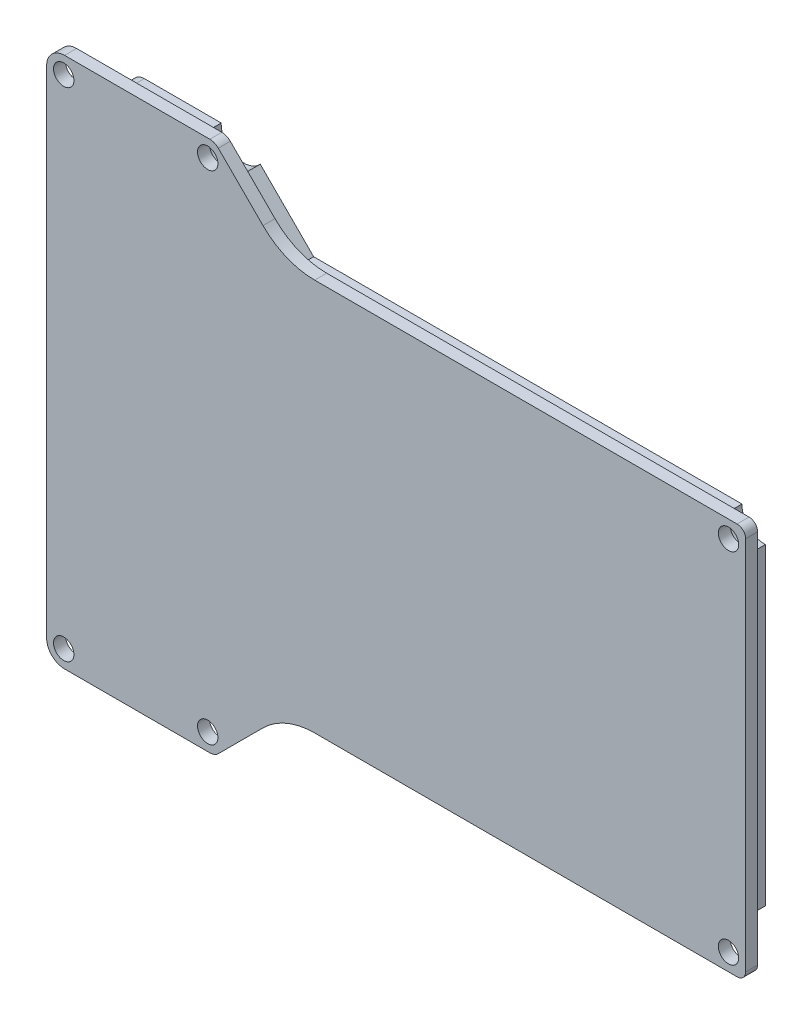
SolidWorks part; units mm, degrees
ref_plane "Front Plane" through (0, 0, 0) normal (0, 0, 1) x (1, 0, 0)
ref_plane "Top Plane" through (0, 0, 0) normal (0, 1, 0) x (1, 0, 0)
ref_plane "Right Plane" through (0, 0, 0) normal (1, 0, 0) x (0, 0, -1)
sketch "Sketch1" plane through (0, 0, 0) normal (0, 0, 1) x (1, 0, 0)
  line L8 (28.7801, -21.4985) -> (21.333, -14.0514)
  line L9 (107.834, -25.0706) -> (37.404, -25.0706)
  line L10 (109.259, -89.0386) -> (109.259, -26.4956)
  line L11 (37.409, -90.4636) -> (107.834, -90.4636)
  line L12 (21.333, -101.4878) -> (28.7851, -94.0357)
  line L13 (-4.3, -102.0736) -> (19.9188, -102.0736)
  line L14 (-7.3, -16.4656) -> (-7.3, -99.0736)
  line L15 (19.9188, -13.4656) -> (-4.3, -13.4656)
  line L16 (16.9123, -100.2696) -> (3, -100.2696) construction
  line L17 (0, -97.2696) -> (0, -18.2696) construction
  line L18 (31.61, -88.6596) -> (22.1833, -98.0863) construction
  line L19 (103.7528, -88.6596) -> (31.61, -88.6596) construction
  line L20 (107.455, -84.9574) -> (107.455, -30.5767) construction
  line L21 (31.605, -26.8746) -> (103.7528, -26.8746) construction
  line L22 (22.1833, -17.4529) -> (31.605, -26.8746) construction
  line L23 (3, -15.2696) -> (16.9123, -15.2696) construction
  line L24 (16.9123, -100.2696) -> (3, -100.2696)
  line L25 (0, -97.2696) -> (0, -18.2696)
  line L26 (31.61, -88.6596) -> (22.1833, -98.0863)
  line L27 (103.7528, -88.6596) -> (31.61, -88.6596)
  line L28 (107.455, -84.9574) -> (107.455, -30.5767)
  line L29 (31.605, -26.8746) -> (103.7528, -26.8746)
  line L30 (22.1833, -17.4529) -> (31.605, -26.8746)
  line L31 (3, -15.2696) -> (16.9123, -15.2696)
  line L32 (3, -16.1696) -> (15.8154, -16.1696)
  line L33 (22.3225, -18.8649) -> (31.2322, -27.7746)
  line L34 (31.2322, -27.7746) -> (102.656, -27.7746)
  line L35 (106.555, -83.8606) -> (106.555, -31.6736)
  line L36 (102.656, -87.7596) -> (31.2372, -87.7596)
  line L37 (31.2372, -87.7596) -> (22.3225, -96.6743)
  line L38 (15.8154, -99.3696) -> (3, -99.3696)
  line L39 (0.9, -97.2696) -> (0.9, -18.2696)
  line L40 (90.115, -68.9796) -> (22, -68.9796) construction
  line L41 (90.115, -44.8746) -> (22, -44.8746) construction
  line L42 (90.115, -68.9796) -> (22, -68.9796) construction
  line L43 (90.115, -44.8746) -> (22, -44.8746) construction
  line L44 (22, -68.9796) -> (0.9, -68.9796) construction
  line L45 (22, -44.8746) -> (0.9, -44.8746) construction
  line L46 (90.115, -44.8746) -> (106.555, -44.8746) construction
  line L47 (90.115, -68.9796) -> (106.555, -68.9796) construction
  line L48 (90.115, -44.3746) -> (104.755, -44.3746)
  line L49 (90.115, -44.3746) -> (22, -44.3746)
  line L50 (22, -44.3746) -> (2.7, -44.3746)
  line L51 (90.115, -69.4796) -> (104.755, -69.4796)
  line L52 (90.115, -69.4796) -> (22, -69.4796)
  line L53 (22, -69.4796) -> (2.7, -69.4796)
  line L54 (90.115, -71.2796) -> (104.755, -71.2796)
  line L55 (90.115, -71.2796) -> (22, -71.2796)
  line L56 (22, -71.2796) -> (2.7, -71.2796)
  line L57 (90.115, -42.5746) -> (104.755, -42.5746)
  line L58 (90.115, -42.5746) -> (22, -42.5746)
  line L59 (22, -42.5746) -> (2.7, -42.5746)
  line L60 (3, -17.9696) -> (14.2636, -17.9696)
  line L61 (22.1471, -21.235) -> (30.4866, -29.5746)
  line L62 (30.4866, -29.5746) -> (101.1041, -29.5746)
  line L63 (104.755, -82.3087) -> (104.755, -71.2796)
  line L64 (101.1041, -85.9596) -> (30.4916, -85.9596)
  line L65 (30.4916, -85.9596) -> (22.1471, -94.3042)
  line L66 (14.2636, -97.5696) -> (3, -97.5696)
  line L67 (2.7, -97.2696) -> (2.7, -71.2796)
  line L68 (104.755, -69.4796) -> (104.755, -44.3746)
  line L69 (104.755, -42.5746) -> (104.755, -33.2255)
  line L70 (104.755, -82.3087) -> (104.755, -33.2255) construction
  line L71 (90.115, -71.2796) -> (106.555, -71.2796) construction
  line L72 (90.115, -69.4796) -> (106.555, -69.4796) construction
  line L73 (90.115, -44.3746) -> (106.555, -44.3746) construction
  line L74 (2.7, -42.5746) -> (2.7, -18.2696)
  line L75 (90.115, -42.5746) -> (106.555, -42.5746) construction
  line L76 (22, -44.3746) -> (0.9, -44.3746) construction
  line L77 (2.7, -69.4796) -> (2.7, -44.3746)
  line L78 (2.7, -97.2696) -> (2.7, -18.2696) construction
  line L79 (22, -42.5746) -> (0.9, -42.5746) construction
  line L80 (22, -71.2796) -> (0.9, -71.2796) construction
  line L82 (22, -69.4796) -> (0.9, -69.4796) construction
  arc A8 (21.333, -14.0514) -> (19.9188, -13.4656) centre (19.9188, -15.4656) ccw
  arc A9 (28.7801, -21.4985) -> (37.404, -25.0706) centre (37.404, -12.8746) ccw
  arc A10 (109.259, -26.4956) -> (107.834, -25.0706) centre (107.834, -26.4956) ccw
  arc A11 (107.834, -90.4636) -> (109.259, -89.0386) centre (107.834, -89.0386) ccw
  arc A12 (37.409, -90.4636) -> (28.7851, -94.0357) centre (37.409, -102.6596) ccw
  arc A13 (19.9188, -102.0736) -> (21.333, -101.4878) centre (19.9188, -100.0736) ccw
  arc A14 (-7.3, -99.0736) -> (-4.3, -102.0736) centre (-4.3, -99.0736) ccw
  arc A15 (-4.3, -13.4656) -> (-7.3, -16.4656) centre (-4.3, -16.4656) ccw
  arc A16 (22.1833, -98.0863) -> (16.9123, -100.2696) centre (19.5655, -99.2206) ccw construction
  arc A17 (0, -97.2696) -> (3, -100.2696) centre (3, -97.2696) ccw construction
  arc A18 (107.455, -84.9574) -> (103.7528, -88.6596) centre (106.406, -87.6106) ccw construction
  arc A19 (103.7528, -26.8746) -> (107.455, -30.5767) centre (106.406, -27.9236) ccw construction
  arc A26 (16.9123, -15.2696) -> (22.1833, -17.4529) centre (19.5655, -16.3186) ccw construction
  arc A27 (3, -15.2696) -> (0, -18.2696) centre (3, -18.2696) ccw construction
  arc A28 (22.1833, -98.0863) -> (16.9123, -100.2696) centre (19.5655, -99.2206) ccw
  arc A29 (0, -97.2696) -> (3, -100.2696) centre (3, -97.2696) ccw
  arc A30 (107.455, -84.9574) -> (103.7528, -88.6596) centre (106.406, -87.6106) ccw
  arc A31 (103.7528, -26.8746) -> (107.455, -30.5767) centre (106.406, -27.9236) ccw
  arc A32 (16.9123, -15.2696) -> (22.1833, -17.4529) centre (19.5655, -16.3186) ccw
  arc A33 (3, -15.2696) -> (0, -18.2696) centre (3, -18.2696) ccw
  circle A34 centre (-4.447, -99.2206) radius 1.5 construction
  circle A35 centre (19.5655, -99.2206) radius 1.5 construction
  circle A36 centre (106.406, -87.6106) radius 1.5 construction
  circle A37 centre (106.406, -27.9236) radius 1.5 construction
  circle A38 centre (19.5655, -16.3186) radius 1.5 construction
  circle A39 centre (-4.447, -16.3186) radius 1.5 construction
  circle A40 centre (-4.447, -99.2206) radius 1.5 construction
  circle A41 centre (19.5655, -99.2206) radius 1.5 construction
  circle A42 centre (106.406, -87.6106) radius 1.5 construction
  circle A43 centre (106.406, -27.9236) radius 1.5 construction
  circle A44 centre (19.5655, -16.3186) radius 1.5 construction
  circle A45 centre (-4.447, -16.3186) radius 1.5 construction
  arc A46 (15.8154, -16.1696) -> (22.3225, -18.8649) centre (19.5655, -16.3186) ccw
  arc A47 (102.656, -27.7746) -> (106.555, -31.6736) centre (106.406, -27.9236) ccw
  arc A48 (106.555, -83.8606) -> (102.656, -87.7596) centre (106.406, -87.6106) ccw
  arc A49 (22.3225, -96.6743) -> (15.8154, -99.3696) centre (19.5655, -99.2206) ccw
  arc A50 (0.9, -97.2696) -> (3, -99.3696) centre (3, -97.2696) ccw
  arc A51 (3, -16.1696) -> (0.9, -18.2696) centre (3, -18.2696) ccw
  circle A52 centre (106.406, -27.9236) radius 1.7
  circle A53 centre (106.406, -87.6106) radius 1.7
  circle A54 centre (19.5655, -99.2206) radius 1.7
  circle A55 centre (-4.447, -99.2206) radius 1.7
  circle A56 centre (-4.447, -16.3186) radius 1.7
  circle A57 centre (19.5655, -16.3186) radius 1.7
  arc A58 (14.2636, -17.9696) -> (22.1471, -21.235) centre (19.5655, -16.3186) ccw
  arc A59 (101.1041, -29.5746) -> (104.755, -33.2255) centre (106.406, -27.9236) ccw
  arc A60 (104.755, -82.3087) -> (101.1041, -85.9596) centre (106.406, -87.6106) ccw
  arc A61 (22.1471, -94.3042) -> (14.2636, -97.5696) centre (19.5655, -99.2206) ccw
  arc A62 (2.7, -97.2696) -> (3, -97.5696) centre (3, -97.2696) ccw
  arc A63 (3, -17.9696) -> (2.7, -18.2696) centre (3, -18.2696) ccw
  point P75 (2.9, -18.2696)
  point P76 (2.9, -97.2696)
  point P85 (105.155, -81.3552)
  point P86 (105.155, -34.179)
  dimension "D1" = 0.9
  dimension "D2" = 0.5
  dimension "D3" = 0.5
  dimension "D4" = 1.8
  dimension "D5" = 1.8
  dimension "D6" = 0.2
  dimension "D7" = 0.2
  dimension "D8" = 0.2
  dimension "D9" = 0.2
  dimension "D10" = 0.2
  dimension "D11" = 0.2
  dimension "D12" = 1.8
extrude "Boss-Extrude1" add sketch "Sketch1" along normal blind 2 contours L15 A15 L14 A14 L13 A13 L12 A12 L11 A11 L10 A10 L9 A9 L8 A8
extrude "Boss-Extrude2" add sketch "Sketch1<3>" against normal blind 4 contours L32 A51 L39 A50 L38 A49 L37 L36 A48 L35 A47 L34 L33 A46 A63 L60 A58 L61 L62 A59 L69 L57 L58 L59 L74 A62 L67 L56 L55 L54 L63 A60 L64 L65 A61 L66 L53 L77 L50 L49 L48 L68 L51 L52 region at (9.4077, -17.5144, 0)
sketch "Sketch1<3>" plane through (0, 0, 0) normal (0, 0, 1) x (1, 0, 0) same geometry as "Sketch1"
extrude "Cut-Extrude1" cut sketch "Sketch1<4>" along normal blind 10 contours A55 | A54 | A56 | A57 | A52 | A53
sketch "Sketch1<4>" plane through (0, 0, 0) normal (0, 0, 1) x (1, 0, 0) same geometry as "Sketch1"
